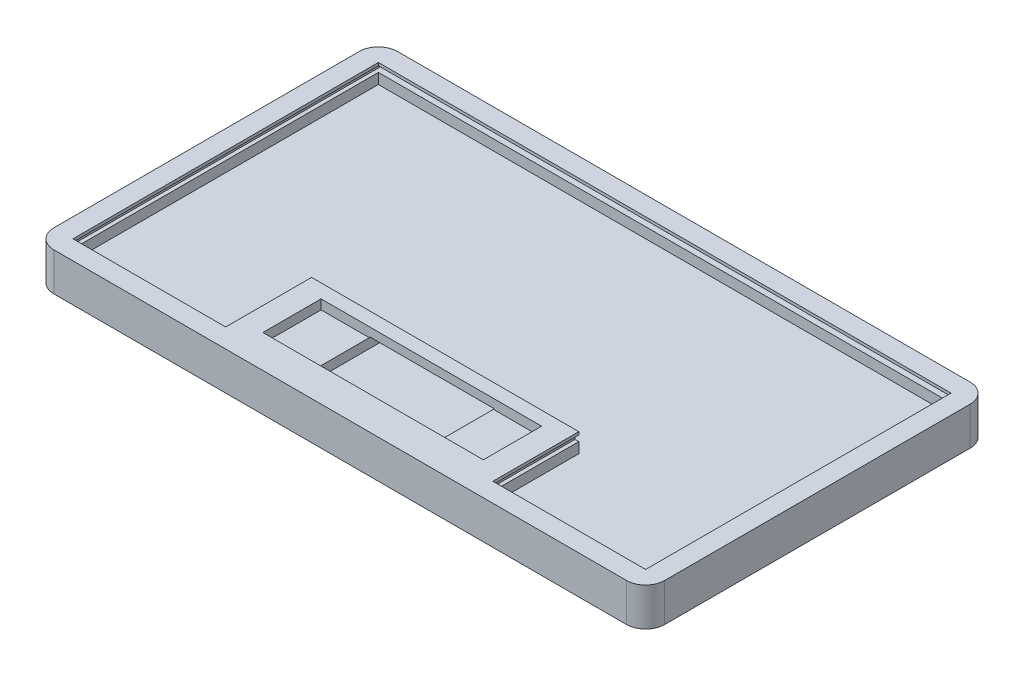
SolidWorks part; units mm, degrees
other "Markup1"
sketch "Sketch6" plane through (-457.2, 50.8, -228.6) normal (0, 1, 0) x (1, 0, 0)
material "Balsa"
ref_plane "Front Plane" through (0, 0, 0) normal (0, 0, 1) x (1, 0, 0)
ref_plane "Top Plane" through (0, 0, 0) normal (0, 1, 0) x (1, 0, 0)
ref_plane "Right Plane" through (0, 0, 0) normal (1, 0, 0) x (0, 0, -1)
sketch "Sketch3" plane through (0, 0, 0) normal (0, 1, 0) x (1, 0, 0)
  line L1 (-406.4, 228.6) -> (406.4, 228.6)
  line L2 (-406.4, 228.6) -> (-406.4, -228.6)
  line L3 (-406.4, -228.6) -> (406.4, -228.6)
  line L4 (406.4, 228.6) -> (406.4, -228.6)
  line L5 (-406.4, 228.6) -> (406.4, -228.6) construction
  line L6 (-406.4, -228.6) -> (406.4, 228.6) construction
  point P0 (0, 0)
  dimension "D1" = 812.8
  dimension "D2" = 457.2
extrude "Boss-Extrude3" add sketch "Sketch3" along normal blind 50.8
sketch "Sketch7" plane through (0, 50.8, 0) normal (0, 1, 0) x (1, 0, 0)
  line L1 (-381, 203.2) -> (381, 203.2)
  line L2 (-381, 203.2) -> (-381, -203.2)
  line L3 (-381, -203.2) -> (381, -203.2)
  line L4 (381, 203.2) -> (381, -203.2)
  line L5 (-381, 203.2) -> (381, -203.2) construction
  line L6 (-381, -203.2) -> (381, 203.2) construction
  point P0 (0, 0)
  dimension "D1" = 762
  dimension "D2" = 406.4
extrude "Cut-Extrude1" cut sketch "Sketch7" against normal blind 25.4
sketch "Sketch8" plane through (0, 25.4, 0) normal (0, 1, 0) x (1, 0, 0)
  line L0 (-381, -203.2) -> (381, -203.2) construction
  line L1 (-177.8, -203.2) -> (177.8, -203.2)
  line L2 (-177.8, -203.2) -> (-177.8, -88.9)
  line L3 (-177.8, -88.9) -> (177.8, -88.9)
  line L4 (177.8, -203.2) -> (177.8, -88.9)
  line L5 (-177.8, -203.2) -> (177.8, -88.9) construction
  line L6 (-177.8, -88.9) -> (177.8, -203.2) construction
  point P0 (0, -146.05)
  dimension "D1" = 355.6
  dimension "D2" = 114.3
extrude "Boss-Extrude7" add sketch "Sketch8" along normal up to surface (25.4 mm away) contours L2 L3 L4 L1 up to face at (0, 50.8, 0)
ref_axis "Axis2" through (0, 0, 228.6) along (0, 0, -1)
ref_plane "Plane2" through (0, 0, 0) normal (1, 0, 0) x (0, 0, -1)
sketch "Sketch23" plane through (-381, 0, 0) normal (1, 0, 0) x (0, 0, -1)
  line L1 (-203.2, 46.99) -> (228.6, 46.99)
  line L2 (-203.2, 46.99) -> (-203.2, 39.37)
  line L3 (-203.2, 39.37) -> (228.6, 39.37)
  line L4 (228.6, 46.99) -> (228.6, 39.37)
  line L5 (-203.2, 46.99) -> (228.6, 39.37) construction
  line L6 (-203.2, 39.37) -> (228.6, 46.99) construction
  line L7 (228.6, 50.8) -> (228.6, 0) construction
  line L9 (-203.2, 25.4) -> (-203.2, 50.8) construction
  line L10 (203.2, 50.8) -> (-203.2, 50.8) construction
  point P0 (12.7, 43.18)
  dimension "D1" = 7.62
  dimension "D2" = 3.81
extrude "Cut-Extrude11" cut sketch "Sketch23" against normal blind 5.08
mirror "Mirror3" about plane through (0, 0, 0) normal (1, 0, 0) of "Cut-Extrude11"
sketch "Sketch24" plane through (0, 0, -228.6) normal (0, 0, -1) x (-1, 0, 0)
  line L1 (-381, 46.99) -> (381, 46.99)
  line L2 (-381, 46.99) -> (-381, 39.37)
  line L3 (-381, 39.37) -> (381, 39.37)
  line L4 (381, 46.99) -> (381, 39.37)
extrude "Cut-Extrude12" cut sketch "Sketch24" against normal blind 81.026
sketch "Sketch26" plane through (0, 0, 203.2) normal (0, 0, -1) x (-1, 0, 0)
  line L0 (-386.08, 46.99) -> (-386.08, 39.37) construction
  line L1 (-386.08, 39.37) -> (-177.8, 39.37)
  line L2 (-386.08, 39.37) -> (-386.08, 46.99)
  line L3 (-386.08, 46.99) -> (-177.8, 46.99)
  line L4 (-177.8, 39.37) -> (-177.8, 46.99)
  line L5 (-386.08, 39.37) -> (-177.8, 46.99) construction
  line L6 (-386.08, 46.99) -> (-177.8, 39.37) construction
  line L10 (-177.8, 50.8) -> (-177.8, 25.4) construction
  point P0 (-281.94, 43.18)
extrude "Cut-Extrude13" cut sketch "Sketch26" against normal blind 5.08
mirror "Mirror4" about plane through (0, 0, 0) normal (1, 0, 0) of "Cut-Extrude13"
sketch "Sketch28" plane through (177.8, 0, 0) normal (1, 0, 0) x (0, 0, -1)
  line L1 (-208.28, 46.99) -> (-88.9, 46.99)
  line L2 (-208.28, 46.99) -> (-208.28, 39.37)
  line L3 (-208.28, 39.37) -> (-88.9, 39.37)
  line L4 (-88.9, 46.99) -> (-88.9, 39.37)
  line L5 (-208.28, 39.37) -> (-208.28, 46.99) construction
  line L9 (-88.9, 50.8) -> (-88.9, 25.4) construction
extrude "Cut-Extrude14" cut sketch "Sketch28" against normal blind 5.08
mirror "Mirror5" about plane through (0, 0, 0) normal (1, 0, 0) of "Cut-Extrude14"
sketch "Sketch30" plane through (0, 50.8, 0) normal (0, 1, 0) x (1, 0, 0)
  line L1 (-146.685, -107.315) -> (146.685, -107.315)
  line L2 (-146.685, -107.315) -> (-146.685, -184.785)
  line L3 (-146.685, -184.785) -> (146.685, -184.785)
  line L4 (146.685, -107.315) -> (146.685, -184.785)
  line L5 (-146.685, -107.315) -> (146.685, -184.785) construction
  line L6 (-146.685, -184.785) -> (146.685, -107.315) construction
  point P0 (0, -146.05)
  dimension "D1" = 293.37
  dimension "D2" = 77.47
extrude "Cut-Extrude16" cut sketch "Sketch30" against normal blind 12.7
sketch "Sketch32" plane through (0, 0, 88.9) normal (0, 0, -1) x (-1, 0, 0)
  line L0 (177.8, 25.4) -> (-177.8, 25.4) construction
  line L1 (-82.55, 25.4) -> (82.55, 25.4)
  line L2 (-82.55, 25.4) -> (-82.55, 39.37)
  line L3 (-82.55, 39.37) -> (82.55, 39.37)
  line L4 (82.55, 25.4) -> (82.55, 39.37)
  line L5 (177.8, 50.8) -> (-177.8, 50.8) construction
  point P7 (0, 39.37)
  point P10 (0, 50.8)
  dimension "D1" = 165.1
extrude "Cut-Extrude19" cut sketch "Sketch32" against normal up to surface (95.885 mm away) and the other way blind 44.45 up to face at (0, 44.45, 184.785)
fillet "Fillet1" radius 25.4 4 edges at (-406.4, 25.4, -228.6) (406.4, 25.4, -228.6) (406.4, 25.4, 228.6) (-406.4, 25.4, 228.6)
